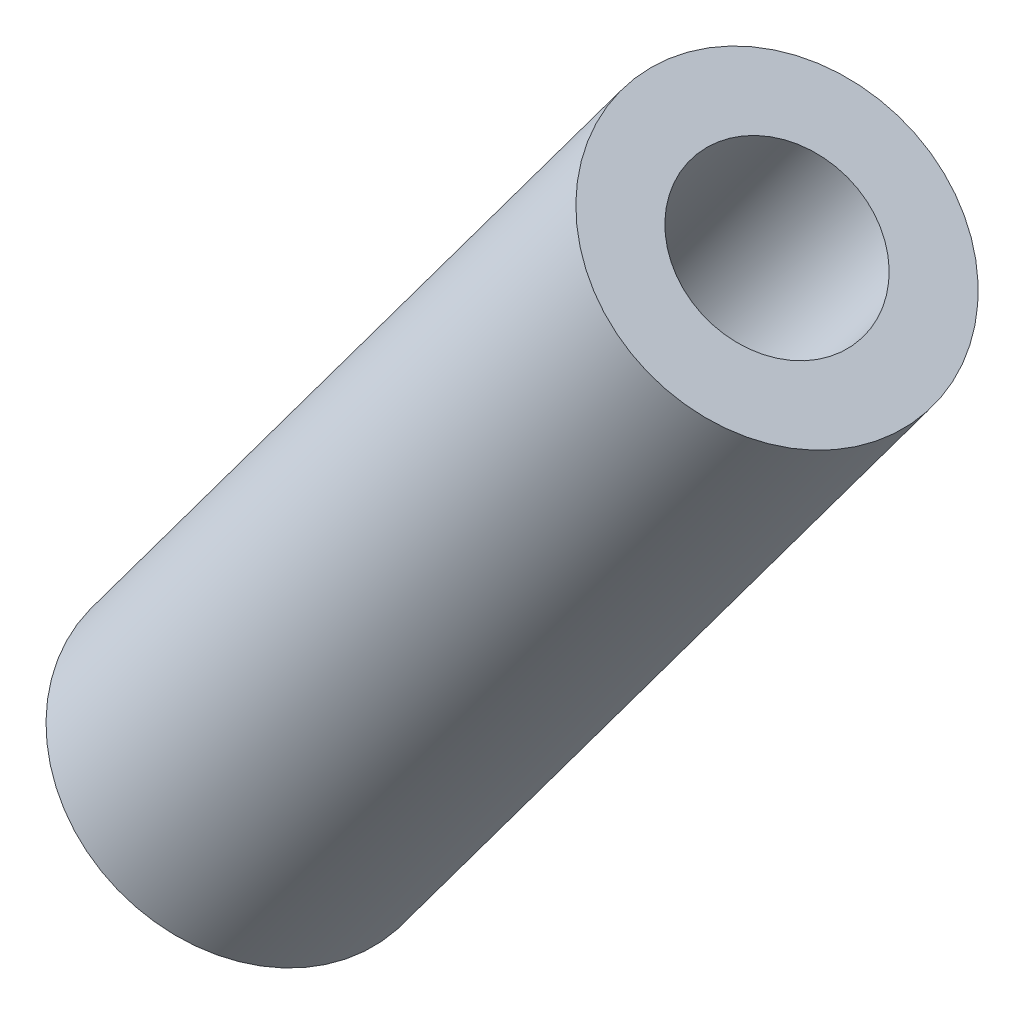
SolidWorks part; units mm, degrees
material "Silicon Rubber"
ref_plane "X-Y Datum" through (0, 0, 0) normal (0, 0, 1) x (1, 0, 0)
ref_plane "X-Z Datum" through (0, 0, 0) normal (0, 1, 0) x (1, 0, 0)
ref_plane "Y-Z Datum" through (0, 0, 0) normal (1, 0, 0) x (0, 0, -1)
sketch3d "3DSketch1"
  line L0 (0, 0, 0) -> (30.2901, 40.7817, 0)
  dimension "D1" = 50.8
sweep "Sweep1" add path "3DSketch1" circular profile diameter 17.9375 parameters "D3"=17.9375
sweep "Cut-Sweep1" cut path "3DSketch1<2>" circular profile diameter 10 parameters "D3"=10
sketch3d "3DSketch1<2>" same geometry as "3DSketch1"
